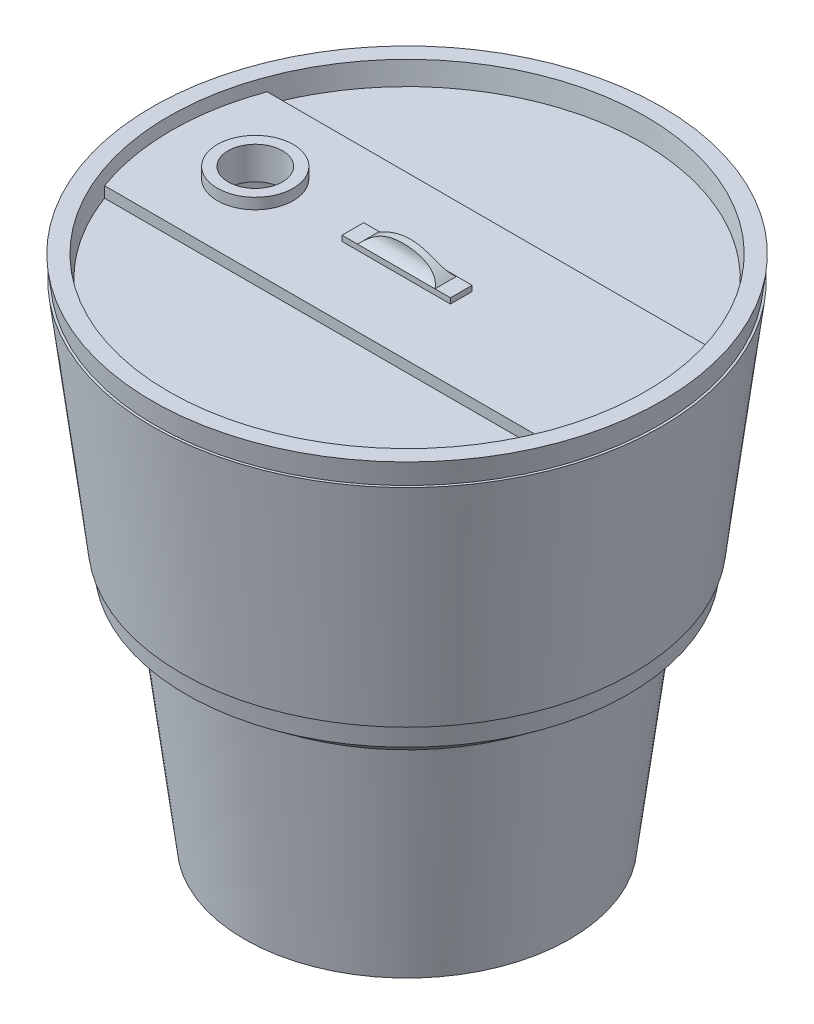
SolidWorks part; units mm, degrees
ref_plane "Front Plane" through (0, 0, 0) normal (0, 0, 1) x (1, 0, 0)
ref_plane "Top Plane" through (0, 0, 0) normal (0, 1, 0) x (1, 0, 0)
ref_plane "Right Plane" through (0, 0, 0) normal (1, 0, 0) x (0, 0, -1)
sketch "Sketch1" plane through (0, 0, 0) normal (0, 0, 1) x (1, 0, 0)
  line L0 (0, 0) -> (0, 80.6957) construction
  line L1 (0, 47.2361) -> (23.5, 47.2361)
  line L2 (23.5, 47.2361) -> (20.375, 22.2361)
  line L3 (20.375, 22.2361) -> (17.5, 20)
  line L4 (17.5, 20) -> (15, 0)
  line L5 (15, 0) -> (0, 0)
  line L6 (0, 47.2361) -> (0, 0)
  dimension "D1" = 47
  dimension "D2" = 25
  dimension "D3" = 20
  dimension "D4" = 30
  dimension "D5" = 35
  dimension "D6" = 135
revolve "Revolve1" add sketch "Sketch1" angle 360 about L0
sketch "Sketch2" plane through (0, 0, 0) normal (0, -1, 0) x (1, 0, 0)
  circle A0 centre (0, 0) radius 13
  dimension "D1" = 26
extrude "Cut-Extrude1" cut sketch "Sketch2" against normal blind 1 draft 45
sketch "Sketch3" plane through (0, 0, 0) normal (0, 0, 1) x (1, 0, 0)
  line L0 (0, 0) -> (0, 53.54) construction
  line L1 (-22.7461, 45.2361) -> (-20.1211, 24.2361)
  line L2 (-23.5, 47.2361) -> (-20.375, 22.2361) construction
  line L3 (20.375, 22.2361) -> (-20.375, 22.2361) construction
  line L4 (23.5, 47.2361) -> (-23.5, 47.2361) construction
  line L5 (-23.4407, 45.1493) -> (-20.8157, 24.1493)
  line L6 (-22.7461, 45.2361) -> (-23.4407, 45.1493)
  line L7 (-20.1211, 24.2361) -> (-20.8157, 24.1493)
  dimension "D1" = 0.5
  dimension "D2" = 2
  dimension "D3" = 2
  dimension "D4" = 0.7
revolve "Cut-Revolve1" cut sketch "Sketch3" angle 360 about L0
revolve "Revolve2" add sketch "Sketch3<2>" angle 360 about L0
sketch "Sketch3<2>" plane through (0, 0, 0) normal (0, 0, 1) x (1, 0, 0) same geometry as "Sketch3"
sketch "Sketch4" plane through (0, 0, 0) normal (0, 0, 1) x (1, 0, 0)
  line L0 (0, 0) -> (0, 66.0811) construction
  line L1 (-15, 0) -> (15, 0) construction
  line L2 (0, 51.679) -> (22.5437, 51.679)
  line L4 (14.1797, 1.5) -> (0, 1.5)
  line L5 (0, 1.5) -> (0, 51.679)
  line L6 (20.1211, 24.2361) -> (22.7461, 45.2361) construction
  line L7 (22.5437, 51.679) -> (18.8091, 21.802)
  line L8 (18.8091, 21.802) -> (16.4922, 20)
  line L9 (16.4922, 20) -> (14.1797, 1.5)
  line L10 (15, 0) -> (17.5, 20) construction
  line L11 (17.5, 20) -> (20.375, 22.2361) construction
  dimension "D1" = 1.5
  dimension "D2" = 1
  dimension "D3" = 1
revolve "Cut-Revolve2" cut sketch "Sketch4" angle 360 about L0
sketch "Sketch5" plane through (0, 0, 0) normal (0, 0, 1) x (1, 0, 0)
  line L0 (0, 45.2361) -> (21.7383, 45.2361)
  line L2 (18.8091, 21.802) -> (21.9883, 47.2361) construction
  line L3 (21.7383, 45.2361) -> (21.6133, 44.2361)
  line L4 (21.6133, 44.2361) -> (0, 44.2361)
  line L7 (0, 0) -> (0, 60.1231) construction
  line L8 (0, 45.2361) -> (0, 44.2361)
  line L9 (23.5, 47.2361) -> (-23.5, 47.2361) construction
  dimension "D1" = 2
  dimension "D2" = 1
revolve "Revolve3" add sketch "Sketch5" angle 360 about L7
sketch "Sketch6" plane through (0, 45.2361, 0) normal (0, 1, 0) x (1, 0, 0)
  line L1 (20.4035, -7.5) -> (-20.4035, -7.5)
  line L2 (20.4035, -7.5) -> (20.4035, 7.5) construction
  line L3 (20.4035, 7.5) -> (-20.4035, 7.5)
  line L4 (-20.4035, -7.5) -> (-20.4035, 7.5) construction
  line L5 (20.4035, -7.5) -> (-20.4035, 7.5) construction
  line L6 (20.4035, 7.5) -> (-20.4035, -7.5) construction
  circle A0 centre (0, 0) radius 21.7383 construction
  arc A1 (20.4035, -7.5) -> (20.4035, 7.5) centre (0, 0) ccw
  circle A2 centre (0, 0) radius 21.7383
  arc A3 (-20.4035, 7.5) -> (-20.4035, -7.5) centre (0, 0) ccw
  point P0 (0, 0)
  dimension "D1" = 15
  dimension "D2" = 0
extrude "Boss-Extrude1" add sketch "Sketch6" along normal blind 1
sketch "Sketch7" plane through (0, 46.2361, 0) normal (0, 1, 0) x (1, 0, 0)
  circle A0 centre (-14, 0) radius 3.5
  dimension "D1" = 7
  dimension "D2" = 14
extrude "Boss-Extrude2" add sketch "Sketch7" along normal blind 1
sketch "Sketch8" plane through (0, 47.2361, 0) normal (0, 1, 0) x (1, 0, 0)
  circle A0 centre (-14, 0) radius 2.5
  dimension "D1" = 5
extrude "Cut-Extrude2" cut sketch "Sketch8" against normal blind 19
sketch "Sketch9" plane through (0, 0, 0) normal (0, 0, 1) x (1, 0, 0)
  line L0 (0, 46.2361) -> (0, 50.7587) construction
  line L1 (-20.4035, 46.2361) -> (20.4035, 46.2361) construction
  line L2 (-5, 46.2361) -> (-5, 46.7361)
  line L3 (-5, 46.7361) -> (-3.5707, 46.7361)
  line L4 (5, 46.2361) -> (5, 46.7361)
  line L5 (5, 46.7361) -> (3.5707, 46.7361)
  line L6 (-5, 46.2361) -> (5, 46.2361)
  arc A0 (-3.5707, 46.7361) -> (3.5707, 46.7361) centre (0, 43.2361) cw
  point P10 (0, 48.2361)
  dimension "D4" = 5
  dimension "D1" = 10
  dimension "D2" = 0.5
  dimension "D3" = 2
extrude "Boss-Extrude3" add sketch "Sketch9" along normal mid plane 2
sketch "Sketch10" plane through (0, 0, 0) normal (1, 0, 0) x (0, 0, -1)
  line L0 (0, 46.2361) -> (0, 49.6676) construction
  line L1 (-1, 46.2361) -> (1, 46.2361) construction
  line L2 (-1, 46.7361) -> (-2, 49.4836)
  line L4 (-1, 46.7361) -> (1, 46.7361) construction
  line L5 (1, 46.7361) -> (2, 49.4836)
  arc A0 (-1, 46.7361) -> (-2, 49.4836) centre (-1.8157, 47.995) ccw
  arc A1 (1, 46.7361) -> (2, 49.4836) centre (1.8157, 47.995) cw
  dimension "D2" = 1.5
  dimension "D1" = 2
  dimension "D3" = 70
extrude "Cut-Extrude3" cut sketch "Sketch10" against normal mid plane 15
fillet "Fillet1" [suppressed] radius 0.5
fillet "Fillet2" [suppressed] radius 0.1
fillet "Fillet3" [suppressed] radius 0.1
